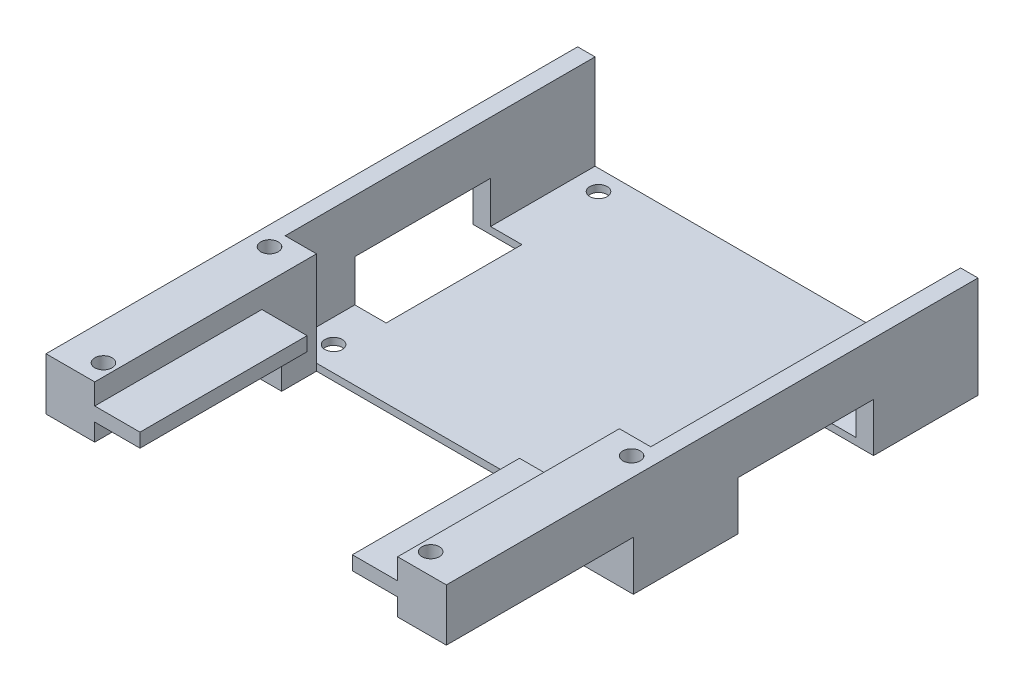
SolidWorks part; units mm, degrees
ref_plane "Front Plane" through (0, 0, 0) normal (0, 0, 1) x (1, 0, 0)
ref_plane "Top Plane" through (0, 0, 0) normal (0, 1, 0) x (1, 0, 0)
ref_plane "Right Plane" through (0, 0, 0) normal (1, 0, 0) x (0, 0, -1)
sketch "Sketch1" plane through (0, 0, 0) normal (0, 1, 0) x (1, 0, 0)
  line L0 (0, 0) -> (0, 76.35) construction
  line L1 (-28.75, 76.35) -> (28.75, 76.35)
  line L2 (28.75, 76.35) -> (28.75, 0)
  line L3 (28.75, 0) -> (21.75, 0)
  line L4 (21.75, 0) -> (21.75, 31.85)
  line L5 (21.75, 31.85) -> (-21.75, 31.85)
  line L6 (-21.75, 31.85) -> (-21.75, 0)
  line L7 (-21.75, 0) -> (-28.75, 0)
  line L8 (-28.75, 0) -> (-28.75, 76.35)
  line L9 (-26.25, 76.35) -> (-26.25, 31.85)
  line L14 (-26.25, 31.85) -> (-21.75, 31.85)
  line L15 (26.25, 76.35) -> (26.25, 31.85)
  line L16 (26.25, 31.85) -> (21.75, 31.85)
  line L17 (28.75, 74.35) -> (30.25, 74.35)
  line L18 (-28.75, 41.35) -> (-26.25, 41.35)
  line L19 (-28.75, 41.35) -> (-28.75, 53.35)
  line L20 (-28.75, 53.35) -> (-26.25, 53.35)
  line L21 (-26.25, 41.35) -> (-26.25, 53.35)
  line L22 (30.25, 68.35) -> (28.75, 68.35)
  line L23 (-30.25, 68.35) -> (-28.75, 68.35)
  line L24 (-28.75, 74.35) -> (-30.25, 74.35)
  arc A0 (30.25, 68.35) -> (30.25, 74.35) centre (30.25, 71.35) ccw
  arc A1 (-30.25, 68.35) -> (-30.25, 74.35) centre (-30.25, 71.35) cw
  point P10 (0, 76.35)
  point P16 (-27.5, 41.35)
  point P17 (-22.85, 73.45)
  point P18 (22.85, 73.45)
  point P23 (22.85, 35.4)
  point P24 (-22.85, 35.4)
  point P25 (23.5, 3)
  point P26 (26, 29.35)
  point P27 (-26, 29.35)
  point P28 (-23.5, 3)
  point P40 (30.25, 71.35)
  point P41 (-30.25, 71.35)
  dimension "D16" = 3
  dimension "D1" = 2.5
  dimension "D2" = 7
  dimension "D3" = 43.5
  dimension "D4" = 31.85
  dimension "D5" = 44.5
  dimension "D6" = 23
  dimension "D7" = 12
  dimension "D8" = 22.85
  dimension "D9" = 38.05
  dimension "D10" = 2.9
  dimension "D11" = 47
  dimension "D12" = 52
  dimension "D13" = 47
  dimension "D14" = 3
  dimension "D15" = 1.5
  dimension "D17" = 2
extrude "Boss-Extrude1" add sketch "Sketch1" along normal blind 1 contours L5 L0 L1 L9 L14 | L0 L5 L16 L15 L1 region at (-13.125, 0, -54.1) region at (13.125, 0, -54.1)
extrude "Boss-Extrude2" add sketch "Sketch1<3>" along normal blind 14.6 contours L18 L8 L7 L6 L14 L9 | L8 L20 L9 L1 | L15 L16 L4 L3 L2 L1 | L20 L8 L18 L9 region at (-27.5, 0, -64.85) region at (25.999, 0, -28.6329) region at (-27.5, 0, -47.35) region at (-25.4666, 0, -17.9154)
sketch "Sketch1<3>" plane through (0, 0, 0) normal (0, 1, 0) x (1, 0, 0) same geometry as "Sketch1"
hole_wizard "Ø2.5 (2.5) Diameter Hole1" positions "Sketch4" profile "Sketch5" hole size "Ø2.5" standard "ANSI Metric" end condition through all
sketch "Sketch4" plane through (0, 0, 0) normal (0, -1, 0) x (-1, 0, 0)
  point P0 (-22.85, 73.45)
  point P3 (22.85, 73.45)
  point P6 (26, 29.35)
  point P9 (22.85, 35.4)
  point P12 (-22.85, 35.4)
  point P15 (-26, 29.35)
  point P18 (-23.5, 3)
  point P21 (23.5, 3)
  point P24 (-30.25, 71.35)
  point P27 (30.25, 71.35)
sketch "Sketch5" plane through (22.85, 0, -73.45) normal (1, 0, 0) x (0, 0, -1)
  line L0 (0, 0) -> (0, 14.6)
  line L1 (0, 14.6) -> (1.25, 14.6)
  line L2 (1.25, 14.6) -> (1.25, 0)
  line L5 (1.25, 0) -> (0, 0)
  line L11 (0, -6.35) -> (0, 107.95) construction
  dimension "Thru Hole Dia." = 2.5
  dimension "Thru Hole Depth" = 14.6
sketch "Sketch6" plane through (0, 0, 0) normal (0, 0, 1) x (1, 0, 0)
  line L0 (-21.75, 14.6) -> (-21.75, 0) construction
  line L5 (0, -1.6497) -> (0, 21.9352) construction
  line L6 (-21.75, 9.6) -> (-15.25, 9.6)
  line L7 (-21.75, 9.6) -> (-21.75, 11.6)
  line L8 (-21.75, 11.6) -> (-15.25, 11.6)
  line L9 (-15.25, 9.6) -> (-15.25, 11.6)
  line L10 (-28.75, 14.6) -> (-28.75, 0) construction
  line L11 (-20.25, 9.6) -> (-21.75, 9.6)
  line L12 (-20.25, 9.6) -> (-20.25, 7.1)
  line L13 (-20.25, 7.1) -> (-21.75, 7.1)
  line L14 (-21.75, 9.6) -> (-21.75, 7.1)
  line L15 (-21.75, 0) -> (-28.75, 0)
  line L16 (-21.75, 0) -> (-21.75, 7.1)
  line L17 (-21.75, 7.1) -> (-28.75, 7.1)
  line L18 (-28.75, 0) -> (-28.75, 7.1)
  line L19 (28.75, 0) -> (28.75, 7.1)
  line L20 (21.75, 7.1) -> (28.75, 7.1)
  line L21 (21.75, 0) -> (21.75, 7.1)
  line L22 (21.75, 0) -> (28.75, 0)
  line L23 (21.75, 9.6) -> (21.75, 7.1)
  line L24 (20.25, 7.1) -> (21.75, 7.1)
  line L25 (20.25, 9.6) -> (20.25, 7.1)
  line L26 (20.25, 9.6) -> (21.75, 9.6)
  line L27 (15.25, 9.6) -> (15.25, 11.6)
  line L28 (21.75, 11.6) -> (15.25, 11.6)
  line L29 (21.75, 9.6) -> (21.75, 11.6)
  line L30 (21.75, 9.6) -> (15.25, 9.6)
  line L31 (-21.75, 14.6) -> (-28.75, 14.6) construction
  line M21 (21.75, 0) -> (28.75, 0)
  line M22 (28.75, 0) -> (28.75, 14.6)
  line M24 (21.75, 14.6) -> (21.75, 0)
  dimension "D1" = 6.5
  dimension "D2" = 3
  dimension "D3" = 2
  dimension "D4" = 2.5
  dimension "D5" = 1.5
extrude "Boss-Extrude3" add sketch "Sketch6" against normal blind 24 contours L30 L26 L28 L27 M24 | L6 L9 L8 L7 region at (-18.5, 10.6, 0) region at (18.5, 10.6, 0)
extrude "Cut-Extrude1" cut sketch "Sketch6<4>" against normal blind 26.85 contours L18 L15 L16 L17 | L20 M24 M21 M22 region at (-25.25, 3.55, 0) region at (25.25, 3.55, 0)
sketch "Sketch6<4>" plane through (0, 0, 0) normal (0, 0, 1) x (1, 0, 0) same geometry as "Sketch6"
sketch "Sketch8" plane through (0, 0, 0) normal (0, -1, 0) x (1, 0, 0)
  line L0 (0, 17.5937) -> (0, -89.2896) construction
  line L1 (-28.75, -61.35) -> (-21.75, -61.35)
  line L2 (-28.75, -61.35) -> (-28.75, -41.85)
  line L3 (-28.75, -41.85) -> (-21.75, -41.85)
  line L4 (-21.75, -61.35) -> (-21.75, -41.85)
  line L6 (-28.75, -76.35) -> (28.75, -76.35) construction
  line L8 (21.75, -61.35) -> (21.75, -41.85)
  line L9 (28.75, -41.85) -> (21.75, -41.85)
  line L10 (28.75, -61.35) -> (28.75, -41.85)
  line L11 (28.75, -61.35) -> (21.75, -61.35)
  line L12 (-28.75, -26.85) -> (-28.75, -76.35) construction
  dimension "D1" = 15
  dimension "D2" = 7
  dimension "D3" = 19.5
extrude "Cut-Extrude2" cut sketch "Sketch8" against normal blind 7
sketch "Sketch9" plane through (0, 0, 0) normal (0, -1, 0) x (1, 0, 0)
  line L0 (-3.6898, -66.9636) -> (-0.7669, -56.1918)
  line L1 (-0.7669, -56.1918) -> (-9.5993, -56.1918)
  line L2 (-9.5993, -56.1918) -> (4.2079, -40.0618)
  line L3 (4.2079, -40.0618) -> (3.001, -51.0446)
  line L4 (3.001, -51.0446) -> (10.9951, -51.0446)
  line L5 (10.9951, -51.0446) -> (-3.6898, -66.9636)
extrude "Cut-Extrude3" cut sketch "Sketch9" against normal blind 0.3
equation "\"D1@Boss-Extrude2\"=16.000000mm-1.4"
